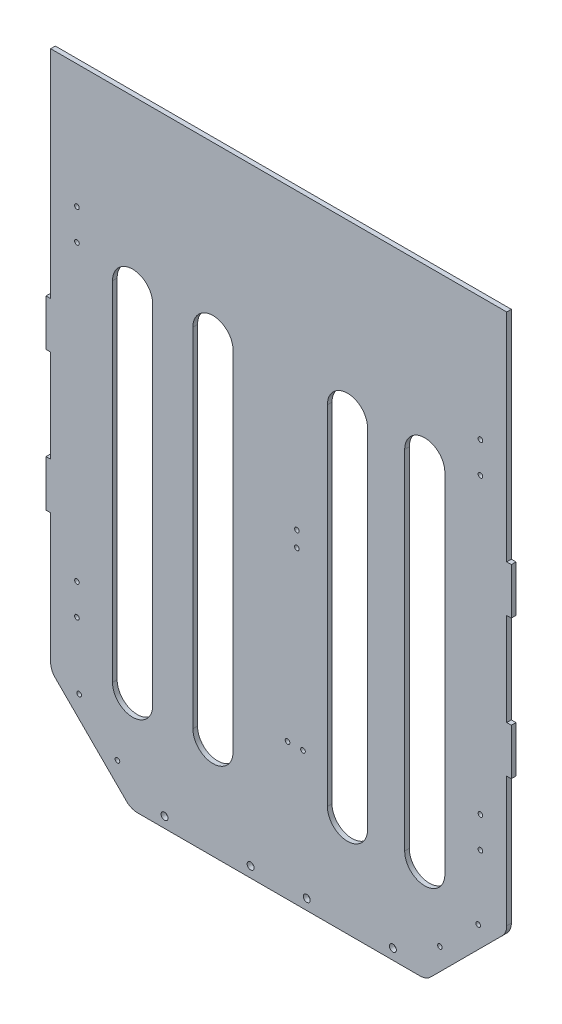
SolidWorks part; units mm, degrees
ref_plane "前视基准面" through (0, 0, 0) normal (0, 0, 1) x (1, 0, 0)
ref_plane "上视基准面" through (0, 0, 0) normal (0, 1, 0) x (1, 0, 0)
ref_plane "右视基准面" through (0, 0, 0) normal (1, 0, 0) x (0, 0, -1)
sketch "草图1" plane through (0, 0, 0) normal (0, 0, 1) x (1, 0, 0)
  line L0 (-147.5, 90) -> (-150.5, 90)
  line L1 (-147.5, 170) -> (147.5, 170)
  line L2 (-147.5, 170) -> (-147.5, 90)
  line L3 (-147.5, -170) -> (147.5, -170)
  line L4 (147.5, 170) -> (147.5, 90)
  line L5 (-147.5, 170) -> (147.5, -170) construction
  line L6 (-147.5, -170) -> (147.5, 170) construction
  line L7 (-150.5, 90) -> (-150.5, 60)
  line L8 (-150.5, 60) -> (-147.5, 60)
  line L9 (-147.5, 60) -> (-147.5, 0)
  line L10 (-147.5, 0) -> (-150.5, 0)
  line L11 (-150.5, 0) -> (-150.5, -30)
  line L12 (-150.5, -30) -> (-147.5, -30)
  line L13 (-147.5, -90) -> (-150.5, -90) construction
  line L14 (-150.5, -90) -> (-150.5, -120) construction
  line L15 (-150.5, -120) -> (-147.5, -120) construction
  line L16 (-147.5, -30) -> (-147.5, -90)
  line L17 (-147.5, -120) -> (-147.5, -170)
  line L18 (0, 0) -> (0, 121.9272) construction
  line L19 (147.5, -90) -> (150.5, -90) construction
  line L20 (150.5, -90) -> (150.5, -120) construction
  line L21 (150.5, -120) -> (147.5, -120) construction
  line L22 (147.5, 0) -> (150.5, 0)
  line L23 (150.5, 0) -> (150.5, -30)
  line L24 (150.5, -30) -> (147.5, -30)
  line L25 (147.5, 90) -> (150.5, 90)
  line L26 (150.5, 90) -> (150.5, 60)
  line L27 (150.5, 60) -> (147.5, 60)
  line L28 (147.5, -120) -> (147.5, -170)
  line L29 (147.5, -30) -> (147.5, -90)
  line L30 (147.5, 60) -> (147.5, 0)
  line L31 (-147.5, -90) -> (-147.5, -120)
  line L32 (147.5, -90) -> (147.5, -120)
  point P0 (0, 0)
  dimension "D1" = 295
  dimension "D2" = 340
  dimension "D3" = 30
  dimension "D4" = 3
  dimension "D5" = 80
  dimension "D6" = 3
  dimension "D7" = 30
  dimension "D8" = 30
  dimension "D9" = 3
  dimension "D10" = 50
  dimension "D11" = 60
extrude "凸台-拉伸1" add sketch "草图1" along normal blind 3
sketch "草图3" plane through (0, 0, 3) normal (0, 0, 1) x (1, 0, 0)
  line L0 (-147.5, -118) -> (-95.5, -170)
  line L1 (-147.5, -30) -> (-147.5, -170) construction
  line L2 (-147.5, -170) -> (147.5, -170) construction
  line L3 (-95.5, -170) -> (-147.5, -170)
  line L4 (-147.5, -170) -> (-147.5, -118)
  line L5 (147.5, -170) -> (147.5, -118)
  line L6 (147.5, -170) -> (147.5, -30) construction
  line L7 (147.5, -118) -> (95.5, -170)
  line L8 (95.5, -170) -> (147.5, -170)
  dimension "D1" = 52
  dimension "D2" = 52
  dimension "D3" = 52
  dimension "D4" = 52
extrude "切除-拉伸2" cut sketch "草图3" against normal through all
fillet "圆角1" [suppressed] radius 5
sketch "草图2" plane through (0, 0, 3) normal (0, 0, 1) x (1, 0, 0)
  line L0 (-95.5, -170) -> (95.5, -170) construction
  line L1 (0, -170) -> (0, -88.9982) construction
  circle A2 centre (73.85, -163.15) radius 2.25 construction
  circle A3 centre (18.15, -163.15) radius 2.25 construction
  circle A4 centre (-73.85, -163.15) radius 2.25 construction
  circle A5 centre (-18.15, -163.15) radius 2.25 construction
  circle A6 centre (11.8005, 40) radius 1.5
  circle A7 centre (11.8005, 30) radius 1.5
  circle A8 centre (73.85, -163.15) radius 2.25 construction
  circle A9 centre (18.15, -163.15) radius 2.25 construction
  circle A10 centre (-73.85, -163.15) radius 2.25 construction
  circle A11 centre (-18.15, -163.15) radius 2.25 construction
  circle A12 centre (-73.85, -163.15) radius 2.25
  circle A13 centre (-18.15, -163.15) radius 2.25
  circle A14 centre (18.15, -163.15) radius 2.25
  circle A15 centre (73.85, -163.15) radius 2.25
  dimension "D1" = 4.5
  dimension "D2" = 4.5
  dimension "D5" = 3
  dimension "D6" = 3
  dimension "D3" = 55.7
  dimension "D4" = 18.15
extrude "切除-拉伸1" cut sketch "草图2" against normal blind 10
sketch "草图4" plane through (0, 0, 3) normal (0, 0, 1) x (1, 0, 0)
  line L0 (147.5, 170) -> (-147.5, 170) construction
  line L1 (147.5, 90) -> (147.5, 170) construction
  line L2 (147.5, -118) -> (147.5, -30) construction
  line L3 (0, 170) -> (0, 113.7599) construction
  circle A0 centre (130.5, 150) radius 1.5
  circle A1 centre (130.5, 130) radius 1.5
  circle A2 centre (130.5, -60) radius 1.5
  circle A3 centre (130.5, -80) radius 1.5
  circle A4 centre (-130.5, -80) radius 1.5
  circle A5 centre (-130.5, -60) radius 1.5
  circle A6 centre (-130.5, 130) radius 1.5
  circle A7 centre (-130.5, 150) radius 1.5
  dimension "D1" = 20
  dimension "D2" = 20
  dimension "D3" = 190
  dimension "D4" = 20
  dimension "D5" = 17
  dimension "D6" = 17
  dimension "D7" = 17
  dimension "D8" = 17
  dimension "D9" = 3
  dimension "D10" = 3
  dimension "D11" = 3
  dimension "D12" = 3
extrude "切除-拉伸3" cut sketch "草图4" against normal through all
sketch "草图5" plane through (0, 0, 3) normal (0, 0, 1) x (1, 0, 0)
  line L0 (-94.5, 120) -> (-94.5, -105) construction
  line L1 (-81.5, 120) -> (-81.5, -105)
  line L2 (-107.5, 120) -> (-107.5, -105)
  line L3 (147.5, 170) -> (-147.5, 170) construction
  line L4 (-147.5, 60) -> (-147.5, 0) construction
  line L5 (-42.5, 120) -> (-42.5, -105) construction
  line L6 (-29.5, 120) -> (-29.5, -105)
  line L7 (-55.5, 120) -> (-55.5, -105)
  line L8 (44.5, 120) -> (44.5, -105) construction
  line L9 (57.5, 120) -> (57.5, -105)
  line L10 (31.5, 120) -> (31.5, -105)
  line L11 (94.5, 120) -> (94.5, -105) construction
  line L12 (107.5, 120) -> (107.5, -105)
  line L13 (81.5, 120) -> (81.5, -105)
  arc A0 (-81.5, 120) -> (-107.5, 120) centre (-94.5, 120) ccw
  arc A1 (-107.5, -105) -> (-81.5, -105) centre (-94.5, -105) ccw
  arc A2 (-29.5, 120) -> (-55.5, 120) centre (-42.5, 120) ccw
  arc A3 (-55.5, -105) -> (-29.5, -105) centre (-42.5, -105) ccw
  arc A4 (57.5, 120) -> (31.5, 120) centre (44.5, 120) ccw
  arc A5 (31.5, -105) -> (57.5, -105) centre (44.5, -105) ccw
  arc A6 (107.5, 120) -> (81.5, 120) centre (94.5, 120) ccw
  arc A7 (81.5, -105) -> (107.5, -105) centre (94.5, -105) ccw
  point P2 (-94.5, 7.5)
  point P14 (-42.5, 7.5)
  point P22 (44.5, 7.5)
  point P29 (94.5, 7.5)
  dimension "D1" = 13
  dimension "D2" = 225
  dimension "D3" = 50
  dimension "D4" = 53
  dimension "D8" = 52
  dimension "D9" = 87
  dimension "D5" = 2
  dimension "D6" = 2
  dimension "D7" = 2
extrude "切除-拉伸4" cut sketch "草图5" against normal through all
sketch "草图6" plane through (0, 0, 3) normal (0, 0, 1) x (1, 0, 0)
  line L0 (31.5, 120) -> (31.5, -105) construction
  line L1 (31.5, 12) -> (57.5, 12)
  line L2 (31.5, 12) -> (31.5, -23)
  line L3 (31.5, -23) -> (57.5, -23)
  line L4 (57.5, 12) -> (57.5, -23)
  line L5 (57.5, -105) -> (57.5, 120) construction
  arc A0 (57.5, 120) -> (31.5, 120) centre (44.5, 120) ccw construction
  dimension "D1" = 35
  dimension "D2" = 108
fillet "圆角3" radius 10 4 edges at (147.5, -118, 1.5) (95.5, -170, 1.5) (-95.5, -170, 1.5) (-147.5, -118, 1.5)
sketch "草图8" plane through (0, 0, 3) normal (0, 0, 1) x (1, 0, 0)
  line L0 (-129.0441, -122.3138) -> (-104.2954, -147.0625) construction
  line L1 (-98.4289, -167.0711) -> (-144.5711, -120.9289) construction
  line L2 (-147.5, -99.7493) -> (147.5, -99.7493) construction
  line L3 (-147.5, -30) -> (-147.5, -113.8579) construction
  line L4 (147.5, -113.8579) -> (147.5, -30) construction
  line L5 (0, -99.7493) -> (0, -54.3911) construction
  line L6 (129.0441, -122.3138) -> (104.2954, -147.0625) construction
  circle A0 centre (-129.0441, -122.3138) radius 1.5
  circle A1 centre (-104.2954, -147.0625) radius 1.5
  circle A2 centre (104.2954, -147.0625) radius 1.5
  circle A3 centre (129.0441, -122.3138) radius 1.5
  dimension "D1" = 3
  dimension "D2" = 3
  dimension "D3" = 10
  dimension "D4" = 35
extrude "切除-拉伸5" cut sketch "草图8" against normal through all
sketch "草图9" plane through (0, 0, 3) normal (0, 0, 1) x (1, 0, 0)
  line L1 (147.5, 170) -> (-147.5, 170)
  line L2 (147.5, 170) -> (147.5, 230)
  line L3 (147.5, 230) -> (-147.5, 230)
  line L4 (-147.5, 170) -> (-147.5, 230)
  dimension "D1" = 60
extrude "凸台-拉伸2" add sketch "草图9" against normal blind 3
sketch "草图10" plane through (0, 0, 0) normal (0, 0, -1) x (-1, 0, 0)
  circle A0 centre (-15.7145, -81.4977) radius 1.5
  circle A1 centre (-5.7145, -81.4977) radius 1.5
extrude "切除-拉伸6" cut sketch "草图10" against normal blind 10
